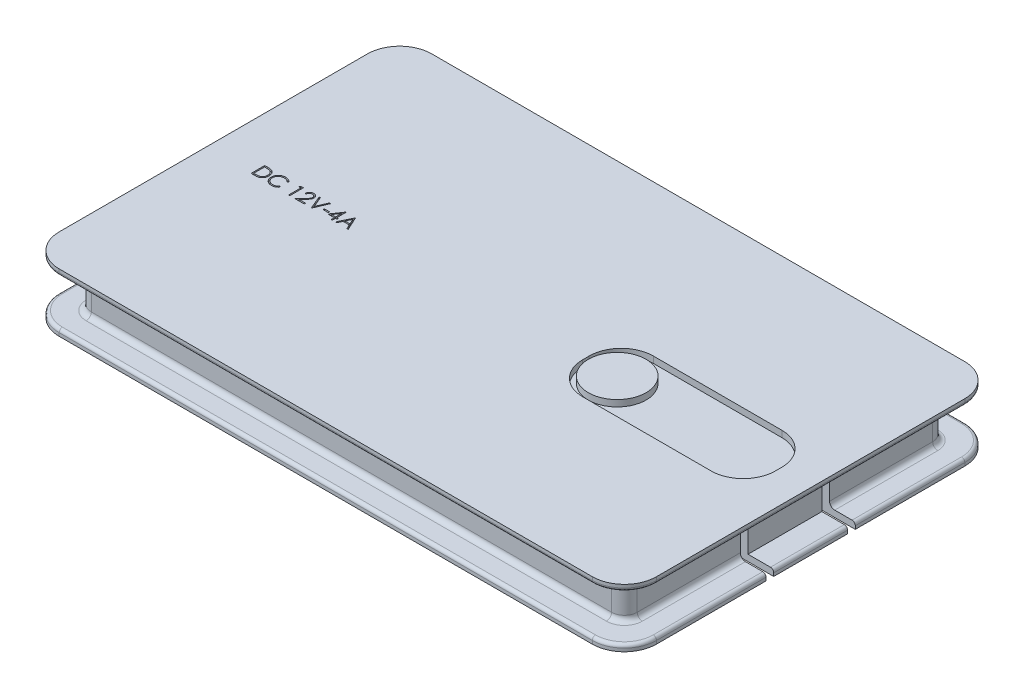
SolidWorks part; units mm, degrees
ref_plane "Front Plane" through (0, 0, 0) normal (0, 0, 1) x (1, 0, 0)
ref_plane "Top Plane" through (0, 0, 0) normal (0, 1, 0) x (1, 0, 0)
ref_plane "Right Plane" through (0, 0, 0) normal (1, 0, 0) x (0, 0, -1)
sketch "Sketch1" plane through (0, 0, 0) normal (0, 1, 0) x (1, 0, 0)
  line L1 (-42.5, -25) -> (42.5, -25)
  line L2 (-42.5, -25) -> (-42.5, 25)
  line L3 (-42.5, 25) -> (42.5, 25)
  line L4 (42.5, -25) -> (42.5, 25)
  line L5 (-42.5, -25) -> (42.5, 25) construction
  line L6 (-42.5, 25) -> (42.5, -25) construction
  point P0 (0, 0)
  dimension "D1" = 50
  dimension "D2" = 85
extrude "Boss-Extrude1" add sketch "Sketch1" along normal blind 9.1
sketch "Sketch2" plane through (0, 0, 25) normal (0, 0, 1) x (1, 0, 0)
  line L0 (42.5, 9.1) -> (42.5, 0) construction
  line L1 (-42.5, 9.1) -> (42.5, 9.1)
  line L2 (-42.5, 9.1) -> (-42.5, 8.1)
  line L3 (-42.5, 8.1) -> (42.5, 8.1)
  line L4 (42.5, 9.1) -> (42.5, 8.1)
  line L6 (-42.5, 0) -> (42.5, 0)
  line L7 (-42.5, 0) -> (-42.5, 1)
  line L8 (-42.5, 1) -> (42.5, 1)
  line L9 (42.5, 0) -> (42.5, 1)
  dimension "D1" = 1
  dimension "D2" = 1
extrude "Boss-Extrude2" add sketch "Sketch2" along normal blind 4
sketch "Sketch3" plane through (0, 0, -25) normal (0, 0, -1) x (-1, 0, 0)
  line L0 (42.5, 9.1) -> (42.5, 0) construction
  line L1 (-42.5, 9.1) -> (42.5, 9.1)
  line L2 (-42.5, 9.1) -> (-42.5, 8.1)
  line L3 (-42.5, 8.1) -> (42.5, 8.1)
  line L4 (42.5, 9.1) -> (42.5, 8.1)
  line L6 (-42.5, 0) -> (42.5, 0)
  line L7 (-42.5, 0) -> (-42.5, 1)
  line L8 (-42.5, 1) -> (42.5, 1)
  line L9 (42.5, 0) -> (42.5, 1)
  dimension "D1" = 1
  dimension "D2" = 1
extrude "Boss-Extrude3" add sketch "Sketch3" along normal blind 4
sketch "Sketch4" plane through (42.5, 0, 0) normal (1, 0, 0) x (0, 0, -1)
  line L1 (-29, 9.1) -> (29, 9.1)
  line L2 (-29, 9.1) -> (-29, 8.1)
  line L3 (-29, 8.1) -> (29, 8.1)
  line L4 (29, 9.1) -> (29, 8.1)
  line L5 (-29, 0) -> (29, 0)
  line L6 (-29, 0) -> (-29, 1)
  line L7 (-29, 1) -> (29, 1)
  line L8 (29, 0) -> (29, 1)
extrude "Boss-Extrude4" add sketch "Sketch4" along normal blind 4
sketch "Sketch5" plane through (-42.5, 0, 0) normal (-1, 0, 0) x (0, 0, 1)
  line L1 (-29, 9.1) -> (29, 9.1)
  line L2 (-29, 9.1) -> (-29, 8.1)
  line L3 (-29, 8.1) -> (29, 8.1)
  line L4 (29, 9.1) -> (29, 8.1)
  line L5 (-29, 0) -> (29, 0)
  line L6 (-29, 0) -> (-29, 1)
  line L7 (-29, 1) -> (29, 1)
  line L8 (29, 0) -> (29, 1)
extrude "Boss-Extrude5" add sketch "Sketch5" along normal blind 4
fillet "Fillet1" radius 5 8 edges at (46.5, 0.5, -29) (46.5, 8.6, -29) (46.5, 0.5, 29) (46.5, 8.6, 29) (-46.5, 0.5, 29) (-46.5, 8.6, 29) (-46.5, 0.5, -29) (-46.5, 8.6, -29)
fillet "Fillet2" radius 2 4 edges
sketch "Sketch6" plane through (0, 9.1, 0) normal (0, 1, 0) x (1, 0, 0)
  line L0 (-43.9424, 18.5595) -> (-5.0489, 4.4034)
  line L1 (-46.5, -24) -> (-46.5, 24) construction
  dimension "D1" = 70
sketch "Sketch7" plane through (0, 0, 0) normal (0, -1, 0) x (1, 0, 0)
  line L0 (-43.9424, -18.5595) -> (-5.0489, -4.4034)
ref_plane "Plane1" through (0.8246, 0, -2.2656) normal (0.342, 0, -0.9397) x (-0.9397, 0, -0.342)
ref_plane "Plane2" through (-19.6966, 0, 54.116) normal (0.342, 0, -0.9397) x (-0.9397, 0, -0.342)
sketch "Sketch8" plane through (-19.6966, 0, 54.116) normal (0.342, 0, -0.9397) x (-0.9397, 0, -0.342)
  line L0 (51.9042, 8.1) -> (35.4872, 8.1) construction
  circle A0 centre (45.9569, 6.9) radius 1.1
  dimension "D1" = 1.2
  dimension "D2" = 2.2
extrude "Cut-Extrude1" cut sketch "Sketch8" along normal blind 66
sketch "Sketch9" plane through (-42.5, 0, 0) normal (-1, 0, 0) x (0, 0, 1)
  line L0 (24, 1) -> (-24, 1) construction
  line L1 (-8.7, 5.95) -> (-0.35, 5.95)
  line L2 (-8.7, 5.95) -> (-8.7, 3.15)
  line L3 (-8.7, 3.15) -> (-0.35, 3.15)
  line L4 (-0.35, 5.95) -> (-0.35, 3.15)
  line L5 (23, 1) -> (23, 8.1) construction
  line L6 (4.65, 5.95) -> (13, 5.95)
  line L7 (4.65, 5.95) -> (4.65, 3.15)
  line L8 (4.65, 3.15) -> (13, 3.15)
  line L9 (13, 5.95) -> (13, 3.15)
  dimension "D1" = 2.8
  dimension "D2" = 8.35
  dimension "D3" = 2.15
  dimension "D4" = 8.35
  dimension "D5" = 5
  dimension "D6" = 10
extrude "Cut-Extrude2" cut sketch "Sketch9" against normal blind 6
sketch "Sketch10" plane through (-36.5, 0, 0) normal (-1, 0, 0) x (0, 0, 1)
  line L1 (-8.2, 5.05) -> (-0.85, 5.05)
  line L2 (-8.2, 5.05) -> (-8.2, 4.05)
  line L3 (-8.2, 4.05) -> (-0.85, 4.05)
  line L4 (-0.85, 5.05) -> (-0.85, 4.05)
  line L5 (-8.7, 5.95) -> (-8.7, 3.15) construction
  line L6 (-0.35, 3.15) -> (-0.35, 5.95) construction
  line L7 (-0.35, 5.95) -> (-8.7, 5.95) construction
  dimension "D1" = 1
  dimension "D2" = 0.5
  dimension "D3" = 0.5
  dimension "D4" = 0.9
extrude "Boss-Extrude6" add sketch "Sketch10" along normal blind 5.5
sketch "Sketch11" plane through (-36.5, 0, 0) normal (-1, 0, 0) x (0, 0, 1)
  line L0 (4.65, 5.95) -> (4.65, 3.15) construction
  line L1 (5.15, 5.05) -> (12.5, 5.05)
  line L2 (5.15, 5.05) -> (5.15, 4.05)
  line L3 (5.15, 4.05) -> (12.5, 4.05)
  line L4 (12.5, 5.05) -> (12.5, 4.05)
  line L5 (13, 3.15) -> (13, 5.95) construction
  line L6 (13, 5.95) -> (4.65, 5.95) construction
  point P6 (13, 4.55)
  dimension "D1" = 1
  dimension "D2" = 0.5
  dimension "D3" = 0.5
  dimension "D4" = 0.9
extrude "Boss-Extrude7" add sketch "Sketch11" along normal blind 5.5
fillet "Fillet3" radius 1 4 edges at (-39.5, 5.95, -0.35) (-39.5, 3.15, -0.35) (-39.5, 3.15, -8.7) (-39.5, 5.95, -8.7)
fillet "Fillet4" radius 1 4 edges at (-39.5, 5.95, 4.65) (-39.5, 3.15, 4.65) (-39.5, 3.15, 13) (-39.5, 5.95, 13)
fillet "Fillet5" radius 0.5 4 edges at (-39.25, 4.05, -8.2) (-39.25, 5.05, -8.2) (-39.25, 4.05, -0.85) (-39.25, 5.05, -0.85)
fillet "Fillet6" radius 0.5 4 edges at (-39.25, 4.05, 12.5) (-39.25, 5.05, 12.5) (-39.25, 4.05, 5.15) (-39.25, 5.05, 5.15)
chamfer "Chamfer1" distance 0.2 angle 45 6 edges at (-42, 4.05, -4.525) (-42, 4.1964, -0.9964) (-42, 4.1964, -8.0536) (-42, 4.9036, -0.9964) (-42, 4.9036, -8.0536) (-42, 5.05, -4.525)
chamfer "Chamfer2" distance 0.2 angle 45 6 edges at (-42, 4.05, 8.825) (-42, 4.1964, 12.3536) (-42, 4.1964, 5.2964) (-42, 4.9036, 12.3536) (-42, 4.9036, 5.2964) (-42, 5.05, 8.825)
fillet "Fillet7" radius 0.1 16 edges at (-42.5, 5.6571, 12.7071) (-42.5, 4.55, 13) (-42.5, 3.4429, 12.7071) (-42.5, 3.15, 8.825) (-42.5, 3.4429, 4.9429) (-42.5, 4.55, 4.65) (-42.5, 5.6571, 4.9429) (-42.5, 5.6571, -0.6429) (-42.5, 4.55, -0.35) (-42.5, 3.4429, -0.6429) (-42.5, 3.15, -4.525) (-42.5, 3.4429, -8.4071) (-42.5, 4.55, -8.7) (-42.5, 5.6571, -8.4071) (-42.5, 5.95, 8.825) (-42.5, 5.95, -4.525)
sketch "Sketch12" plane through (42.5, 0, 0) normal (1, 0, 0) x (0, 0, -1)
  line L0 (-23, 8.1) -> (23, 8.1) construction
  line L1 (-6.95, 8.1) -> (-5.75, 8.1)
  line L2 (-6.95, 8.1) -> (-6.95, 1)
  line L3 (-6.95, 1) -> (-5.75, 1)
  line L4 (-5.75, 8.1) -> (-5.75, 1)
  line L5 (23, 1) -> (-23, 1) construction
  line L6 (-24, 8.1) -> (24, 8.1) construction
  line L7 (5.75, 8.1) -> (6.95, 8.1)
  line L8 (5.75, 8.1) -> (5.75, 1)
  line L9 (5.75, 1) -> (6.95, 1)
  line L10 (6.95, 8.1) -> (6.95, 1)
  point P14 (0, 8.1)
  dimension "D1" = 11.5
  dimension "D2" = 1.2
  dimension "D3" = 1.2
  dimension "D4" = 5.75
extrude "Cut-Extrude3" cut sketch "Sketch12" against normal blind 20
sketch "Sketch13" plane through (0, 9.1, 0) normal (0, 1, 0) x (1, 0, 0)
  line L0 (46.5, 24) -> (46.5, -24) construction
  line L1 (11.5, 5.5089) -> (41.5, 5.5089)
  line L2 (11.5, 5.5089) -> (11.5, -5.4911)
  line L3 (11.5, -5.4911) -> (41.5, -5.4911)
  line L4 (41.5, 5.5089) -> (41.5, -5.4911)
  dimension "D1" = 11
  dimension "D2" = 5
  dimension "D3" = 30
extrude "Cut-Extrude5" cut sketch "Sketch13" against normal blind 1
fillet "Fillet9" radius 5 4 edges at (11.5, 8.6, 5.4911) (11.5, 8.6, -5.5089) (41.5, 8.6, 5.4911) (41.5, 8.6, -5.5089)
sketch "Sketch14" plane through (0, 8.1, 0) normal (0, 1, 0) x (1, 0, 0)
  circle A0 centre (16.3774, 0) radius 4.5
  dimension "D1" = 9
extrude "Boss-Extrude8" add sketch "Sketch14" along normal blind 1
sketch "Sketch16" plane through (0, 9.1, 0) normal (0, 1, 0) x (1, 0, 0)
  text T0 "DC 12V-4A" font "Century Gothic" height in points 8
extrude "Cut-Extrude6" cut sketch "Sketch16" against normal blind 0.3
fillet "Fillet10" radius 0.8 18 edges at (42.5, 1, 14.975) (41.9142, 1, 24.4142) (0, 1, 25) (-41.9142, 1, 24.4142) (42.5, 1, -14.975) (41.9142, 1, -24.4142) (0, 1, -25) (-41.9142, 1, -24.4142) (41.9142, 8.1, -24.4142) (41.9142, 8.1, 24.4142) (-41.9142, 8.1, 24.4142) (-41.9142, 8.1, -24.4142) (-42.5, 1, 0)
fillet "Fillet11" radius 0.5 16 edges at (-45.0355, 1, 27.5355) (0, 1, 29) (45.0355, 1, 27.5355) (46.5, 1, 0) (45.0355, 1, -27.5355) (0, 1, -29) (-45.0355, 1, -27.5355) (-45.0355, 8.1, -27.5355) (0, 8.1, -29) (45.0355, 8.1, -27.5355) (46.5, 8.1, 0) (45.0355, 8.1, 27.5355) (0, 8.1, 29) (-45.0355, 8.1, 27.5355) (-46.5, 1, 0) (-46.5, 8.1, 0)
fillet "Fillet12" radius 0.3 4 edges at (32.9, 8.1, -6.95) (32.5, 8.1, -5.75) (32.5, 8.1, 5.75) (32.9, 8.1, 6.95)
sketch "Sketch17" plane through (0, 1, 0) normal (0, 1, 0) x (1, 0, 0)
  line L0 (22.5, -6.95) -> (43.3, -6.95) construction
  line L1 (38.5, -6.95) -> (50.125, -6.95)
  line L2 (38.5, -6.95) -> (38.5, -5.75)
  line L3 (38.5, -5.75) -> (50.125, -5.75)
  line L4 (50.125, -6.95) -> (50.125, -5.75)
  line L5 (22.5, 5.75) -> (42.5, 5.75) construction
  line L6 (38.5, 5.75) -> (55.0683, 5.75)
  line L7 (38.5, 5.75) -> (38.5, 6.95)
  line L8 (38.5, 6.95) -> (55.0683, 6.95)
  line L9 (55.0683, 5.75) -> (55.0683, 6.95)
  line L10 (22.5, -6.95) -> (22.5, -5.75) construction
  line L11 (22.5, 5.75) -> (22.5, 6.95) construction
  dimension "D1" = 16
  dimension "D2" = 16
extrude "Cut-Extrude7" cut sketch "Sketch17" against normal blind 10
fillet "Fillet13" radius 0.3 4 edges at (38.5, 0.5, -6.95) (38.5, 0.5, -5.75) (38.5, 0.5, 5.75) (38.5, 0.5, 6.95)
